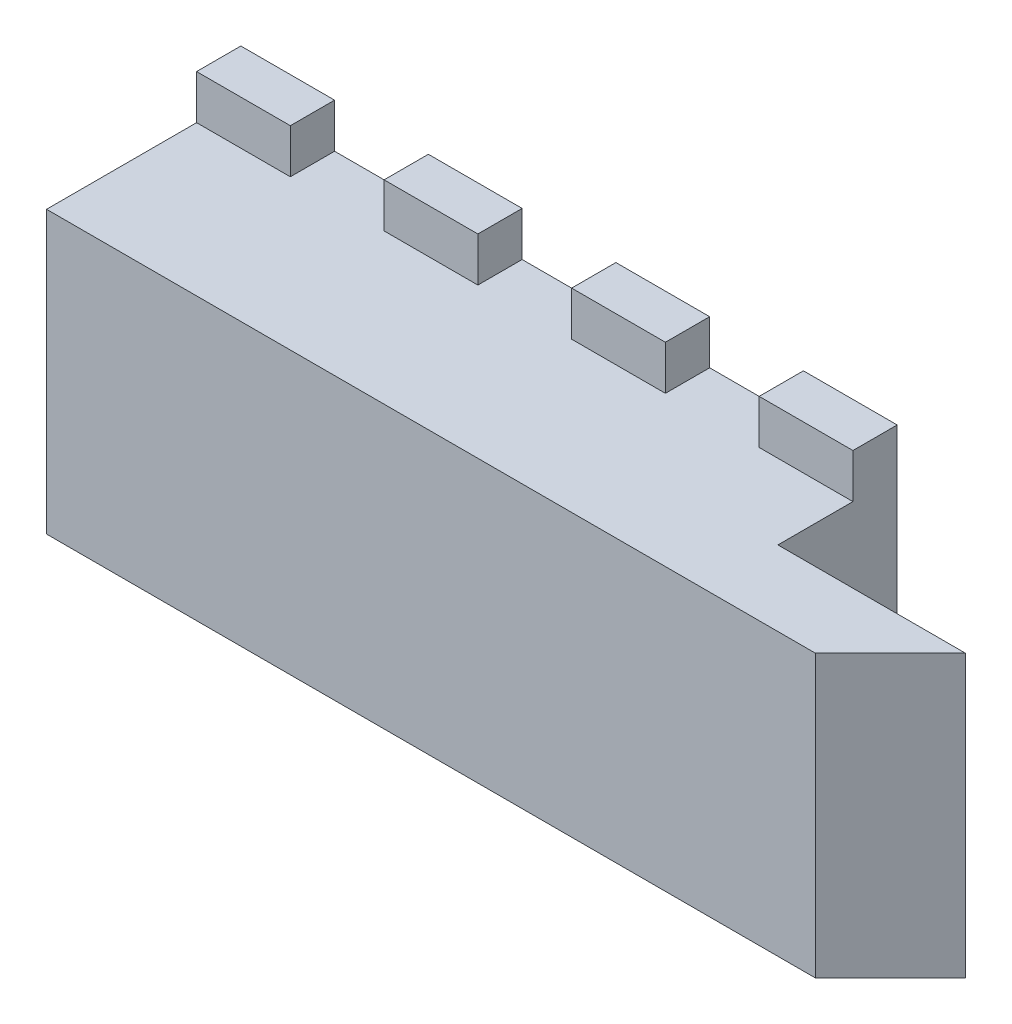
SolidWorks part; units mm, degrees
ref_plane "Front Plane" through (0, 0, 0) normal (0, 0, 1) x (1, 0, 0)
ref_plane "Top Plane" through (0, 0, 0) normal (0, 1, 0) x (1, 0, 0)
ref_plane "Right Plane" through (0, 0, 0) normal (1, 0, 0) x (0, 0, -1)
sketch "Sketch1" plane through (0, 0, 0) normal (0, 0, 1) x (1, 0, 0)
  line L1 (-22.225, -9.525) -> (22.225, -9.525)
  line L2 (-22.225, -9.525) -> (-22.225, 9.525)
  line L3 (-22.225, 9.525) -> (22.225, 9.525)
  line L4 (22.225, -9.525) -> (22.225, 9.525)
  line L5 (-22.225, -9.525) -> (22.225, 9.525) construction
  line L6 (-22.225, 9.525) -> (22.225, -9.525) construction
  point P0 (0, 0)
  dimension "D1" = 19.05
  dimension "D2" = 44.45
extrude "Body" add sketch "Sketch1" along normal blind 2.9972
sketch "Sketch2" plane through (0, 9.525, 0) normal (0, 1, 0) x (1, 0, 0)
  line L0 (22.225, 0) -> (-22.225, 0) construction
  line L1 (-22.225, 0) -> (-15.875, 0)
  line L2 (-22.225, 0) -> (-22.225, -2.9972)
  line L3 (-22.225, -2.9972) -> (-15.875, -2.9972)
  line L4 (-15.875, 0) -> (-15.875, -2.9972)
  line L5 (22.225, -2.9972) -> (-22.225, -2.9972) construction
  line L7 (-22.225, -2.9972) -> (-22.225, 0) construction
  dimension "D1" = 6.35
extrude "Tab" add sketch "Sketch2" along normal blind 2.9972
ref_plane "Tab Midplane" [suppressed] through (-12.7, 0, 0) normal (-1, 0, 0) x (0, 0, 1)
ref_plane "Body Horizontal Midplane" through (0, 0, 0) normal (0, 1, 0) x (1, 0, 0)
ref_plane "Body Vertical Midplane" through (0, 0, 0) normal (-1, 0, 0) x (0, 0, 1)
pattern_linear "LPattern1" count 4 spacing 12.7 along (1, 0, 0) of "Tab"
mirror "Mirror1" about plane through (0, 0, 0) normal (0, 1, 0) of "LPattern1"
sketch "Sketch3" plane through (0, 0, 2.9972) normal (0, 0, 1) x (1, 0, 0)
  line L0 (22.225, -12.5222) -> (22.225, 12.5222) construction
  line L1 (-22.225, 9.525) -> (22.225, 9.525)
  line L2 (-22.225, 9.525) -> (-22.225, -9.525)
  line L3 (-22.225, -9.525) -> (22.225, -9.525)
  line L4 (22.225, 9.525) -> (22.225, -9.525)
  line L5 (-22.225, 9.525) -> (22.225, -9.525) construction
  line L6 (-22.225, -9.525) -> (22.225, 9.525) construction
  line L7 (9.525, -9.525) -> (15.875, -9.525) construction
  point P1 (0, 0)
extrude "Boss-Extrude1" add sketch "Sketch3" along normal blind 10.16
sketch "Sketch4" plane through (22.225, 0, 0) normal (1, 0, 0) x (0, 0, -1)
  line L0 (-13.1572, 9.525) -> (-2.9972, 9.525) construction
  line L1 (-13.1572, 9.525) -> (-8.0772, 9.525)
  line L2 (-13.1572, 9.525) -> (-13.1572, -9.525)
  line L3 (-13.1572, -9.525) -> (-8.0772, -9.525)
  line L4 (-8.0772, 9.525) -> (-8.0772, -9.525)
  line L5 (-13.1572, 9.525) -> (-8.0772, -9.525) construction
  line L6 (-13.1572, -9.525) -> (-8.0772, 9.525) construction
  line L8 (-13.1572, -9.525) -> (-13.1572, 9.525) construction
  line L9 (-13.1572, -9.525) -> (-2.9972, -9.525) construction
  point P0 (-10.6172, 0)
  dimension "D1" = 5.08
extrude "Boss-Extrude2" add sketch "Sketch4" along normal blind 12.7
chamfer "Chamfer1" distance 5.08 angle 45 1 edges at (34.925, 0, 13.1572)
